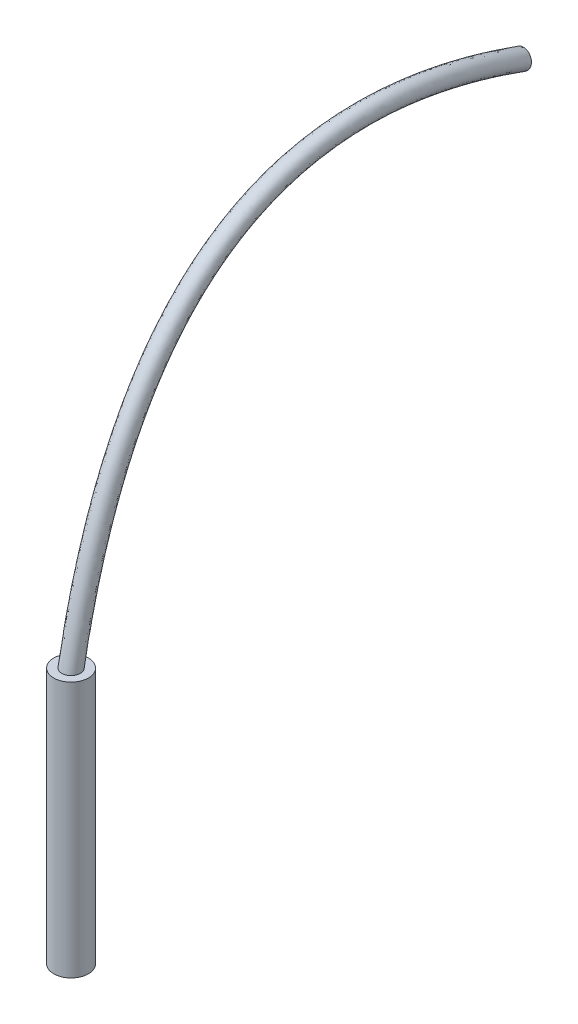
SolidWorks part; units mm, degrees
ref_plane "Front Plane" through (0, 0, 0) normal (0, 0, 1) x (1, 0, 0)
ref_plane "Top Plane" through (0, 0, 0) normal (0, 1, 0) x (1, 0, 0)
ref_plane "Right Plane" through (0, 0, 0) normal (1, 0, 0) x (0, 0, -1)
sketch "Sketch1" plane through (0, 0, 0) normal (0, 1, 0) x (1, 0, 0)
  circle A0 centre (0, 0) radius 2.75
  dimension "D1" = 5.5
extrude "Boss-Extrude1" add sketch "Sketch1" along normal blind 40.64 contours A0
sketch "Sketch2" plane through (0, 0, 0) normal (1, 0, 0) x (0, 0, -1)
  line L0 (2.75, 40.64) -> (-2.75, 40.64) construction
  spline S0 degree 2 poles (0, 40.64) (12.5024, 109.964) (71.518, 88.5742) knots 0 0 0 1 1 1
sketch "Sketch17" plane through (0, 40.64, 0) normal (0, 1, 0) x (1, 0, 0)
  circle A0 centre (0, 0) radius 1.4762
sweep "Sweep2" add profiles "Sketch17" path "Sketch2"
